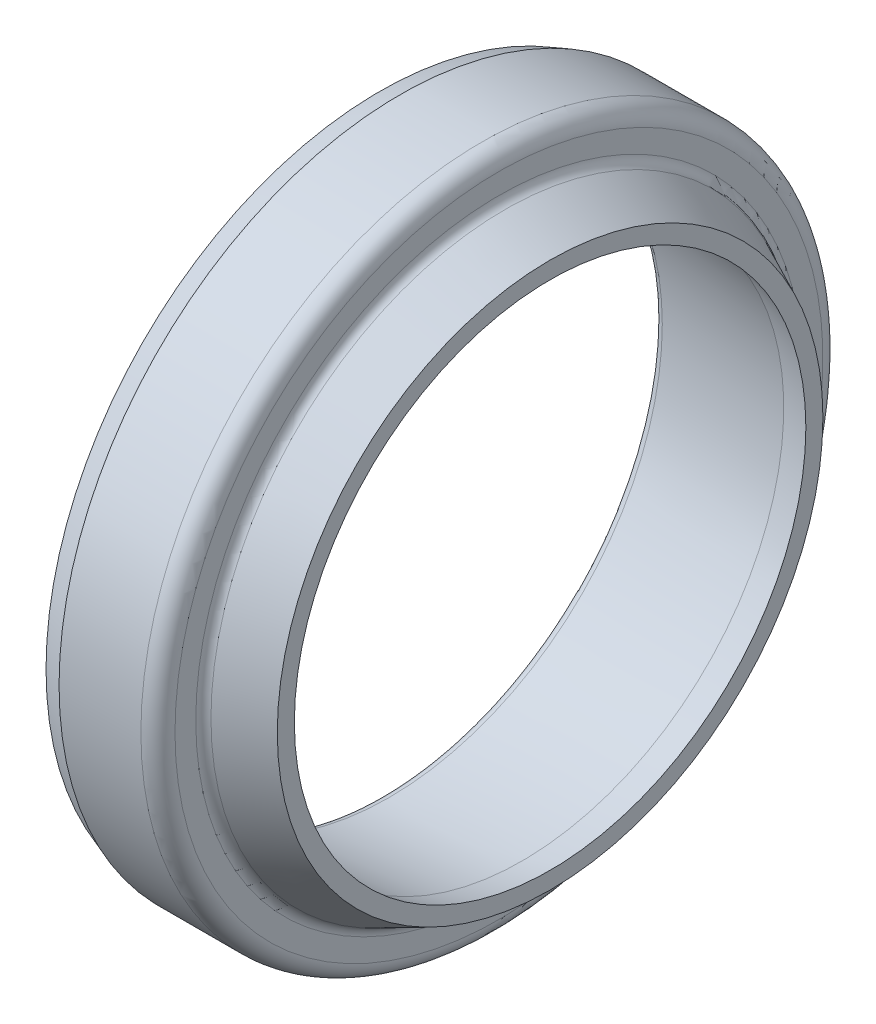
SolidWorks part; units mm, degrees
material "EPDM 60 Durometer"
ref_plane "Front" through (0, 0, 0) normal (0, 0, 1) x (1, 0, 0)
ref_plane "Top" through (0, 0, 0) normal (0, 1, 0) x (1, 0, 0)
ref_plane "Right" through (0, 0, 0) normal (1, 0, 0) x (0, 0, -1)
ref_axis "Axis1" through (-84.4107, 0, 0) along (1, 0, 0)
ref_axis "Axis2" through (0, 64.3378, 0) along (0, -1, 0)
ref_axis "Axis3" through (0, 0, -102.329) along (0, 0, 1)
sketch "Sketch1" plane through (0, 0, 0) normal (0, 0, 1) x (1, 0, 0)
  line L0 (0, 0) -> (9.8194, 0) construction
  line L1 (0, 16.0808) -> (0, 19.5632)
  line L2 (0, 19.5632) -> (1.2, 20)
  line L3 (1.2, 20) -> (7, 20)
  line L4 (7, 20) -> (7, 17.3989)
  line L5 (7, 17.3989) -> (10, 16)
  line L6 (10, 16) -> (10, 15)
  line L7 (10, 15) -> (8.3534, 15.35)
  line L8 (8.3534, 15.35) -> (0, 16.0808)
  dimension "D1" = 15
  dimension "D2" = 10
  dimension "D3" = 160
  dimension "D4" = 5
  dimension "D5" = 12
  dimension "D6" = 4.65
  dimension "D7" = 1
  dimension "D8" = 25
  dimension "D9" = 7
  dimension "D10" = 1.2
  dimension "D11" = 8.3534
revolve "Revolve1" add sketch "Sketch1" angle 360 about L0
fillet "Fillet1" radius 0.6 2 edges at (0, 0, 16.0808) (7, 0, 17.3989)
fillet "Fillet2" radius 1 1 edges at (7, 0, 20)
